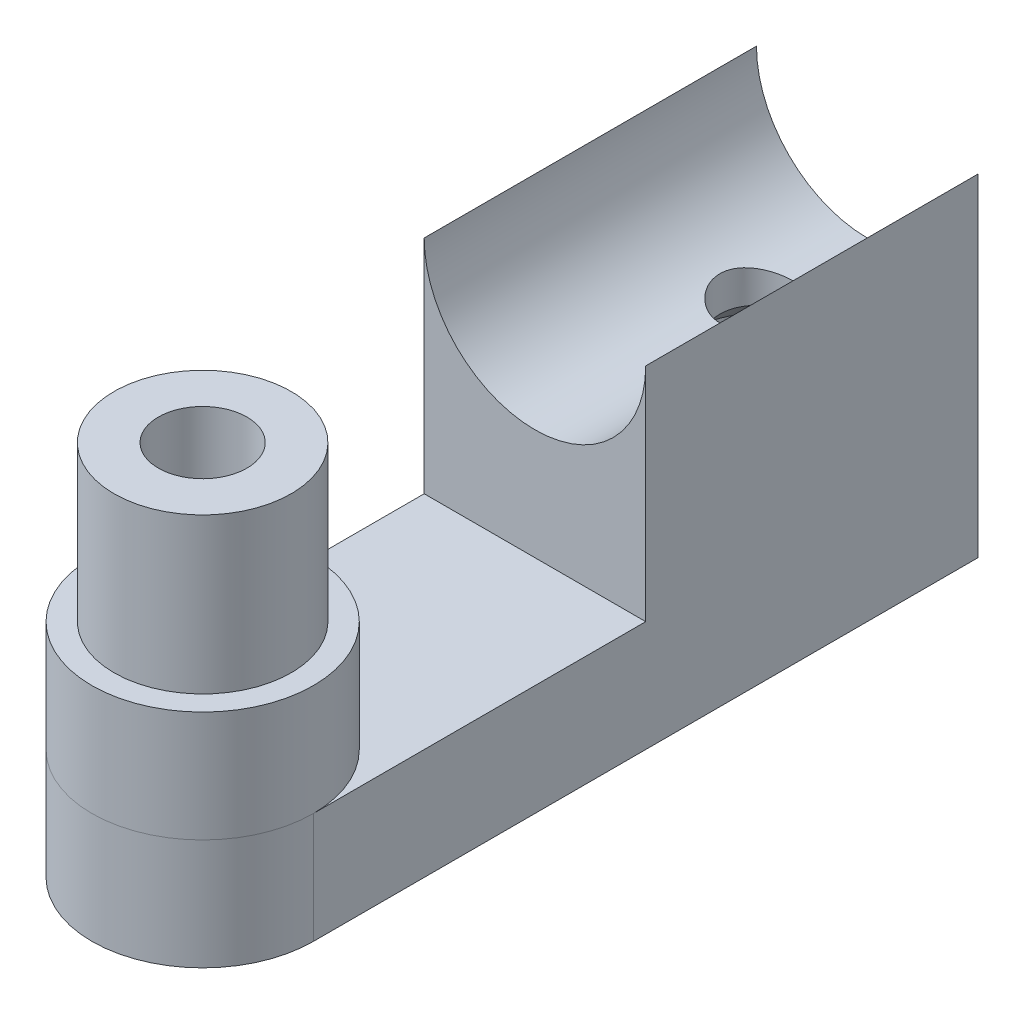
SolidWorks part; units mm, degrees
ref_plane "Front Plane" through (0, 0, 0) normal (0, 0, 1) x (1, 0, 0)
ref_plane "Top Plane" through (0, 0, 0) normal (0, 1, 0) x (1, 0, 0)
ref_plane "Right Plane" through (0, 0, 0) normal (1, 0, 0) x (0, 0, -1)
sketch "Sketch2" plane through (0, 0, 0) normal (0, 1, 0) x (1, 0, 0)
  circle A0 centre (0, 0) radius 4
  dimension "D1" = 8
extrude "Boss-Extrude1" add sketch "Sketch2" along normal blind 7
sketch "Sketch3" plane through (0, 0, 0) normal (0, -1, 0) x (1, 0, 0)
  circle A0 centre (0, 0) radius 5
  dimension "D1" = 10
extrude "Boss-Extrude2" add sketch "Sketch3" along normal blind 5
chamfer "Chamfer1" [suppressed] distance 0.5 angle 45
sketch "Sketch4" plane through (0, 7, 0) normal (0, 1, 0) x (1, 0, 0)
  circle A0 centre (0, 0) radius 1.65
  dimension "D1" = 3.3
extrude "Cut-Extrude1" cut sketch "Sketch4" against normal up to surface (12 mm away) up to face at (0, -5, -5)
sketch "Sketch5" plane through (0, 7, 0) normal (0, -1, 0) x (1, 0, 0)
  circle A0 centre (0, 0) radius 2
  dimension "D1" = 4
extrude "Cut-Extrude2" cut sketch "Sketch5" along normal blind 5
sketch "Sketch7" plane through (0, -5, 0) normal (0, -1, 0) x (1, 0, 0)
  line L0 (-5, 0) -> (-5, -30)
  line L1 (-5, -30) -> (5, -30)
  line L2 (5, -30) -> (5, 0)
  circle A0 centre (0, 0) radius 5 construction
  circle A3 centre (0, 0) radius 5
  arc A4 (5, 0) -> (-5, 0) centre (0, 0) ccw
  dimension "D1" = 30
  dimension "D2" = 0
extrude "Boss-Extrude3" add sketch "Sketch7" along normal blind 5 separate body
sketch "Sketch8" plane through (0, -5, 0) normal (0, 1, 0) x (1, 0, 0)
  line L0 (-5, 0) -> (-5, 30) construction
  line L1 (5, 30) -> (-5, 30)
  line L2 (5, 30) -> (5, 15)
  line L3 (5, 15) -> (-5, 15)
  line L4 (-5, 30) -> (-5, 15)
  dimension "D1" = 15
extrude "Boss-Extrude4" add sketch "Sketch8" along normal blind 10
sketch "Sketch9" plane through (0, 0, -30) normal (0, 0, -1) x (-1, 0, 0)
  line L0 (-5, 5) -> (5, 5) construction
  line L2 (-5, 5) -> (5, 5)
  arc A0 (-5, 5) -> (5, 5) centre (0, 5) ccw
extrude "Cut-Extrude3" cut sketch "Sketch9" against normal up to surface (15 mm away) up to face at (0, 0, -15)
sketch "Sketch10" plane through (0, -10, 0) normal (0, -1, 0) x (1, 0, 0)
  line L0 (-5, -30) -> (5, -30) construction
  circle A0 centre (0, -25) radius 2.75
  point P4 (0, 0)
  dimension "D1" = 5.5
  dimension "D2" = 5
extrude "Cut-Extrude4" cut sketch "Sketch10" against normal blind 7.5
sketch "Sketch11" plane through (0, -2.5, 0) normal (0, -1, 0) x (1, 0, 0)
  circle A0 centre (0, -25) radius 1.65
  circle A1 centre (0, -25) radius 2.75 construction
  dimension "D1" = 3.3
extrude "Cut-Extrude5" cut sketch "Sketch11" against normal through all
chamfer "Chamfer2" distance 1.2 angle 45 1 edges at (0, -2.5, -26.65)
